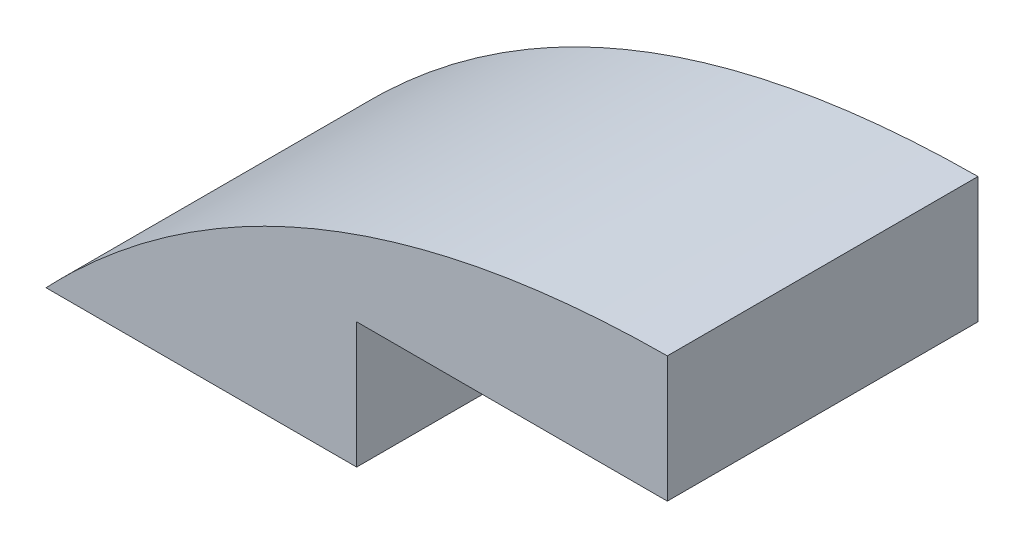
SolidWorks part; units mm, degrees
ref_plane "Front Plane" through (0, 0, 0) normal (0, 0, 1) x (1, 0, 0)
ref_plane "Top Plane" through (0, 0, 0) normal (0, 1, 0) x (1, 0, 0)
ref_plane "Right Plane" through (0, 0, 0) normal (1, 0, 0) x (0, 0, -1)
sketch "Sketch2" plane through (0, 0, 0) normal (0, 1, 0) x (1, 0, 0)
  line L1 (0, 0) -> (7.9, 0)
  line L2 (0, 0) -> (0, 7.9)
  line L3 (0, 7.9) -> (7.9, 7.9)
  line L4 (7.9, 0) -> (7.9, 7.9)
  dimension "D1" = 7.9
  dimension "D2" = 7.9
extrude "Boss-Extrude1" add sketch "Sketch2" along normal blind 3.2
sketch "Sketch3" plane through (0, 3.2, 0) normal (0, 1, 0) x (1, 0, 0)
  line L1 (7.9, 7.9) -> (15.8, 7.9)
  line L2 (7.9, 7.9) -> (7.9, 0)
  line L3 (7.9, 0) -> (15.8, 0)
  line L4 (15.8, 7.9) -> (15.8, 0)
  dimension "D1" = 7.9
extrude "Boss-Extrude2" add sketch "Sketch3" along normal blind 3.2 separate body
sketch "Sketch4" plane through (0, 0, -7.9) normal (0, 0, -1) x (-1, 0, 0)
  line L0 (-15.8, 6.4) -> (0, 6.4)
  line L1 (0, 6.4) -> (0, 0)
  spline S0 degree 2 poles (-15.8, 6.4) (-6.036, 6.3402) (0, 0) knots 0 0 0 1 1 1
  point P2 (-2.26, 2.2976)
  point P4 (-1.5918, 1.6197)
  point P5 (-2.6882, 2.0618)
  point P6 (-2.4411, 2.417)
  point P7 (-2.5956, 2.3244)
  point P10 (-1.8852, 1.753)
sketch "Sketch7" plane through (7.9, 0, 0) normal (-1, 0, 0) x (0, 0, 1)
  line L1 (0, 3.2) -> (-7.9, 3.2)
  line L2 (0, 3.2) -> (0, 6.4)
  line L3 (0, 6.4) -> (-7.9, 6.4)
  line L4 (-7.9, 3.2) -> (-7.9, 6.4)
extrude "Boss-Extrude5" add sketch "Sketch7" along normal blind 7.2
extrude "Cut-Extrude2" cut sketch "Sketch4" against normal blind 8.2
